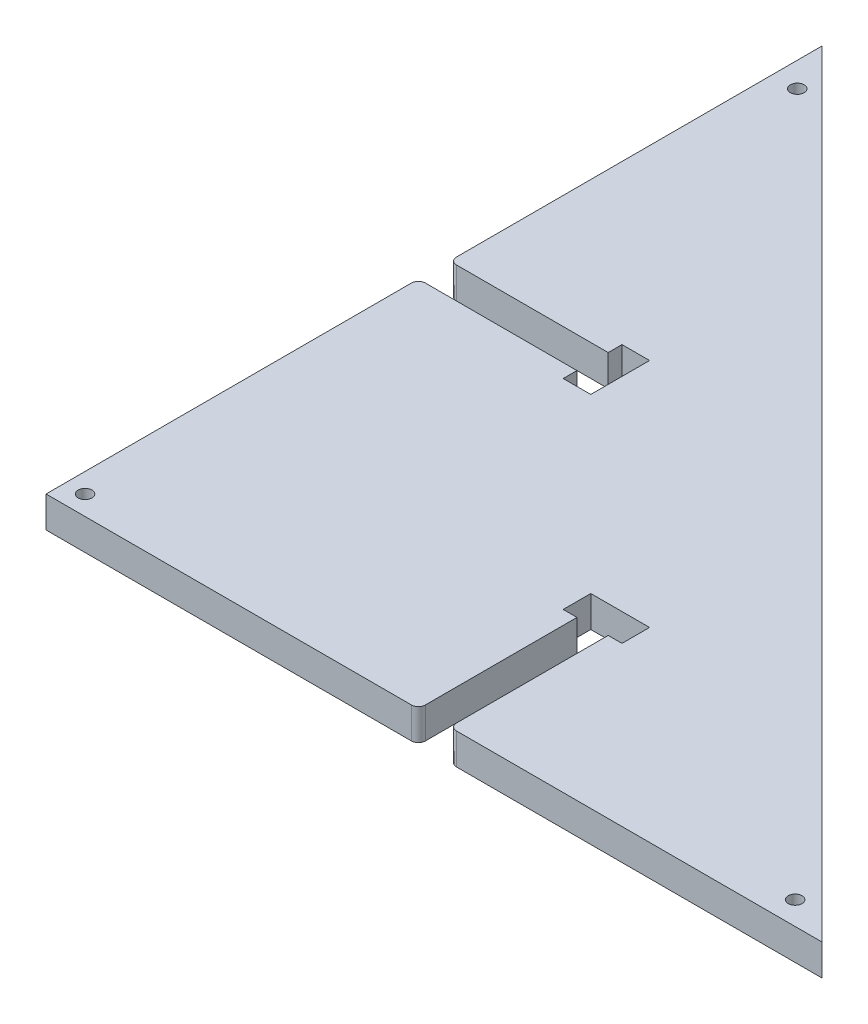
SolidWorks part; units mm, degrees
ref_plane "Front Plane" through (0, 0, 0) normal (0, 0, 1) x (1, 0, 0)
ref_plane "Top Plane" through (0, 0, 0) normal (0, 1, 0) x (1, 0, 0)
ref_plane "Right Plane" through (0, 0, 0) normal (1, 0, 0) x (0, 0, -1)
sketch "Sketch2" plane through (0, 0, 0) normal (0, 1, 0) x (1, 0, 0)
  line L0 (-31.3973, -33.4506) -> (180.5527, -33.4506)
  line L1 (-31.3973, -33.4506) -> (-31.3973, 178.4994)
  line L2 (-31.3973, 416.5494) -> (418.6027, -33.4506)
  line L3 (-31.3973, -33.4506) -> (193.6027, 191.5494) construction
  line L4 (193.6027, 191.5494) -> (193.6027, -33.4506) construction
  line L5 (193.6027, 191.5494) -> (-66.3973, 191.5494) construction
  line L6 (76.5777, 184.0494) -> (76.5777, 169.0494)
  line L7 (-31.3973, -33.4506) -> (-31.3973, 178.4994)
  line L8 (163.6027, 74.5244) -> (173.6027, 74.5244)
  line L9 (60.5777, 200.5994) -> (-27.3973, 200.5994)
  line L10 (202.6527, 58.5244) -> (202.6527, -29.4506)
  line L11 (60.5777, 182.4994) -> (-27.3973, 182.4994)
  line L12 (173.6027, 74.5244) -> (210.6527, 74.5244)
  line L13 (210.6527, 74.5244) -> (210.6527, 58.5244)
  line L14 (210.6527, 58.5244) -> (202.6527, 58.5244)
  line L15 (176.5527, 58.5244) -> (176.5527, 74.5244)
  line L16 (176.5527, 74.5244) -> (163.6027, 74.5244)
  line L17 (184.5527, 58.5244) -> (176.5527, 58.5244)
  line L18 (184.5527, 58.5244) -> (184.5527, -29.4506)
  line L19 (206.6527, -33.4506) -> (418.6027, -33.4506)
  line L20 (76.5777, 169.0494) -> (76.5777, 174.4994)
  line L21 (76.5777, 174.4994) -> (60.5777, 174.4994)
  line L22 (60.5777, 174.4994) -> (60.5777, 182.4994)
  line L23 (60.5777, 208.5994) -> (76.5777, 208.5994)
  line L24 (76.5777, 208.5994) -> (76.5777, 184.0494)
  line L25 (60.5777, 200.5994) -> (60.5777, 208.5994)
  line L26 (-48.8973, 451.5494) -> (211.1027, -68.4506) construction
  line L27 (-31.3973, 204.5994) -> (-31.3973, 416.5494)
  line L28 (-87.5918, 201.3819) -> (439.7971, -43.283) construction
  arc A0 (202.6527, -29.4506) -> (206.6527, -33.4506) centre (206.6527, -29.4506) ccw
  arc A1 (180.5527, -33.4506) -> (184.5527, -29.4506) centre (180.5527, -29.4506) ccw
  arc A2 (-27.3973, 182.4994) -> (-31.3973, 178.4994) centre (-27.3973, 178.4994) ccw
  circle A3 centre (-20.0836, -22.1369) radius 4
  arc A4 (-31.3973, 204.5994) -> (-27.3973, 200.5994) centre (-27.3973, 204.5994) ccw
  circle A5 centre (-17.0865, 387.9278) radius 4
  circle A6 centre (389.5743, -19.9838) radius 4
  point P2 (13.6027, 8.5494)
  point P6 (183.6027, 226.5494)
  point P9 (206.1027, 226.5494)
  point P11 (14.6027, 11.5494)
  point P12 (202.6527, -33.4506)
  point P13 (-31.3973, 184.0494)
  point P14 (13.6027, 14.5494)
  point P15 (13.6027, 12.5494)
  point P16 (-33.3973, 12.5494)
  point P17 (-31.3973, 199.0494)
  dimension "D9" = 8
  dimension "D10" = 8
  dimension "D15" = 8
  dimension "D16" = 8
  dimension "D20" = 8
  dimension "D22" = 8
  dimension "D24" = 8
  dimension "D3" = 450
  dimension "D5" = 215.95
  dimension "D6" = 225
  dimension "D1" = 18.1
  dimension "D2" = 9.05
  dimension "D4" = 18.1
  dimension "D7" = 107.975
  dimension "D8" = 107.975
  dimension "D17" = 9.05
  dimension "D11" = 16
  dimension "D12" = 8
  dimension "D13" = 8
  dimension "D14" = 16
  dimension "D18" = 8
  dimension "D19" = 8
  dimension "D21" = 16
  dimension "D23" = 32
  dimension "D25" = 32
extrude "Boss-Extrude1" add sketch "Sketch2" along normal blind 18.1 contours L7 A4 L9 L6 L11 A2 L1 L0 A1 L18 L17 L15 L8 L12 L13 L14 L10 A0 L19 L2 region at (118.9684, 0, -116.9154)
equation "\"D5@Sketch2\"=\"D3@Sketch2\"/2-(\"D4@Sketch2\"/2)"
equation "\"D6@Sketch2\"=\"D3@Sketch2\"/2"
equation "\"D1@Sketch2\"=\"D4@Sketch2\""
equation "\"D2@Sketch2\"=\"D1@Sketch2\"/2"
equation "\"D10@Sketch2\"=\"D9@Sketch2\""
equation "\"D15@Sketch2\"=\"D9@Sketch2\""
equation "\"D16@Sketch2\"=\"D9@Sketch2\""
equation "\"D7@Sketch2\"=\"D6@Sketch2\"/2-(\"D17@Sketch2\"/2)"
equation "\"D8@Sketch2\"=\"D6@Sketch2\"/2-(\"D17@Sketch2\"/2)"
equation "\"D17@Sketch2\"=\"D4@Sketch2\"/2"
equation "\"spessore\"= 18.10mm"
equation "\"larghezza\"= 450mm"
equation "\"punta_fresa\"= 8mm"
equation "\"D4@Sketch2\"=\"spessore\""
equation "\"D9@Sketch2\"=\"punta_fresa\""
equation "\"D11@Sketch2\"=\"punta_fresa\"*2"
equation "\"D12@Sketch2\"=\"punta_fresa\""
equation "\"D13@Sketch2\"=\"punta_fresa\""
equation "\"D3@Sketch2\"=\"larghezza\""
equation "\"D1@Boss-Extrude1\"=\"spessore\""
equation "\"D14@Sketch2\"=\"punta_fresa\"*2"
equation "\"D18@Sketch2\"=\"punta_fresa\""
equation "\"D19@Sketch2\"=\"punta_fresa\""
equation "\"D20@Sketch2\"=\"punta_fresa\""
equation "\"D21@Sketch2\"=\"punta_fresa\"*2"
equation "\"D22@Sketch2\"=\"punta_fresa\""
equation "\"D23@Sketch2\"=\"punta_fresa\"*4"
equation "\"D24@Sketch2\"=\"punta_fresa\""
equation "\"D25@Sketch2\"=\"punta_fresa\"*4"
